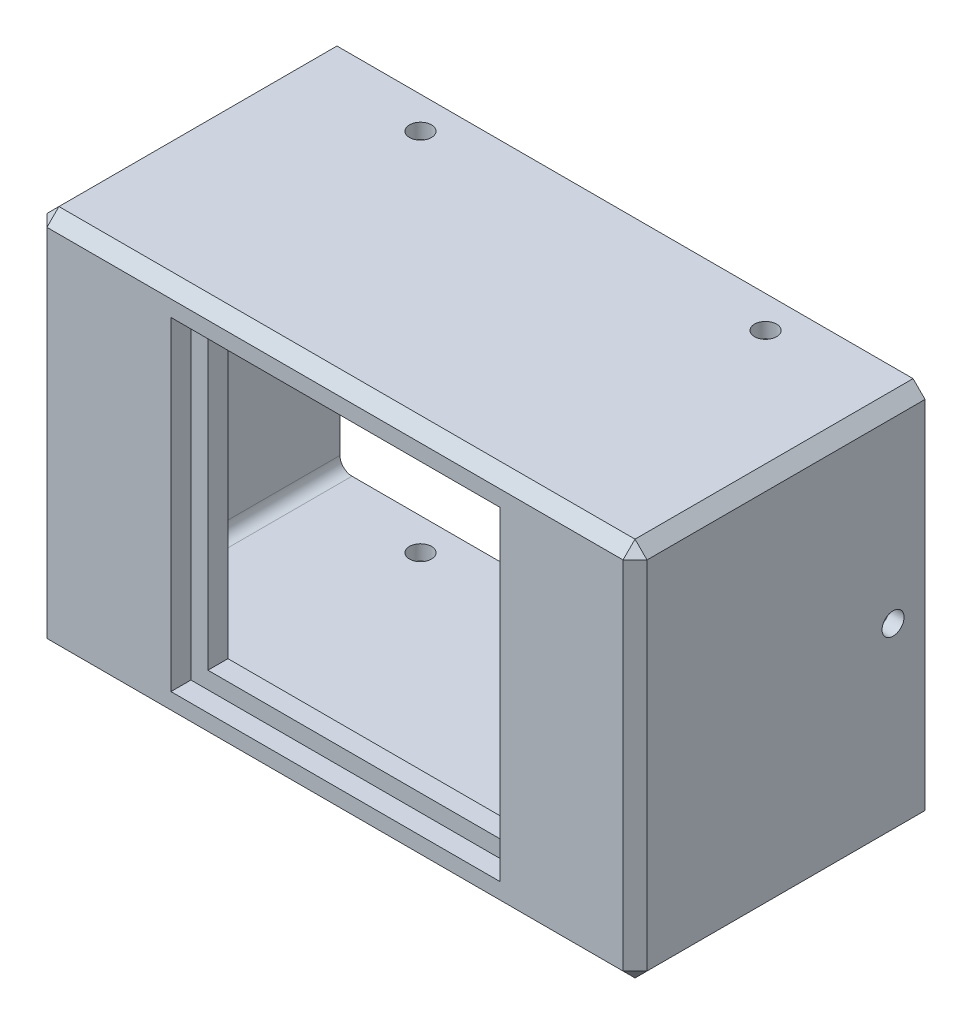
SolidWorks part; units mm, degrees
ref_plane "Plan de face" through (0, 0, 0) normal (0, 0, 1) x (1, 0, 0)
ref_plane "Plan de dessus" through (0, 0, 0) normal (0, 1, 0) x (1, 0, 0)
ref_plane "Plan de droite" through (0, 0, 0) normal (1, 0, 0) x (0, 0, -1)
sketch "Esquisse1" plane through (0, 0, 0) normal (0, 0, 1) x (1, 0, 0)
  line L1 (30, 19) -> (-30, 19)
  line L2 (30, 19) -> (30, -19)
  line L3 (30, -19) -> (-30, -19)
  line L4 (-30, 19) -> (-30, -19)
  line L5 (30, 19) -> (-30, -19) construction
  line L6 (30, -19) -> (-30, 19) construction
  point P0 (0, 0)
  point P6 (0, 0)
  dimension "D1" = 60
  dimension "D2" = 38
extrude "BASE" add sketch "Esquisse1" along normal blind 4
sketch "Esquisse2" plane through (0, 0, 4) normal (0, 0, 1) x (1, 0, 0)
  line L0 (-21.2, 0) -> (26.8, 0) construction
  line L1 (26.8, 16.5) -> (-21.2, 16.5) construction
  line L2 (26.8, 16.5) -> (26.8, -16.5) construction
  line L3 (26.8, -16.5) -> (-21.2, -16.5) construction
  line L4 (-21.2, 16.5) -> (-21.2, -16.5) construction
  line L5 (26.8, 16.5) -> (-21.2, -16.5) construction
  line L6 (26.8, -16.5) -> (-21.2, 16.5) construction
  line L7 (-14.7, 14.5) -> (14.8, 14.5)
  line L8 (-14.7, 14.5) -> (-14.7, -14.5)
  line L9 (-14.7, -14.5) -> (14.8, -14.5)
  line L10 (14.8, 14.5) -> (14.8, -14.5)
  line L11 (30, -19) -> (30, 19) construction
  point P0 (0, 0)
  dimension "D1" = 33
  dimension "D2" = 48
  dimension "D3" = 6.5
  dimension "D4" = 2
  dimension "D5" = 2
  dimension "D6" = 12
  dimension "D7" = 3.2
extrude "Screen" cut sketch "Esquisse2" against normal up to surface (4 mm away) up to face at (0, 0, 0)
sketch "Esquisse5" plane through (0, 0, 0) normal (0, 0, -1) x (-1, 0, 0)
  line L0 (2.2, 0) -> (-2.2, 0) construction
  line L1 (21.2, 16.5) -> (-26.8, 16.5) construction
  line L2 (21.2, 16.5) -> (21.2, -16.5) construction
  line L3 (21.2, -16.5) -> (-26.8, -16.5) construction
  line L4 (-26.8, 16.5) -> (-26.8, -16.5) construction
  line L5 (21.2, 16.5) -> (-26.8, -16.5) construction
  line L6 (21.2, -16.5) -> (-26.8, 16.5) construction
  line L8 (-2.8, 16.5) -> (-2.8, -16.5) construction
  circle A1 centre (-24.3, 14) radius 2.25
  circle A2 centre (-24.3, -14) radius 2.25
  circle A3 centre (18.7, -14) radius 2.25
  circle A4 centre (18.7, 14) radius 2.25
  point P0 (-0.8987, -1.3072)
  dimension "D3" = 4.5
  dimension "D1" = 48
  dimension "D2" = 33
  dimension "D4" = 2.5
  dimension "D5" = 2.5
extrude "Inserts_M3" cut sketch "Esquisse5" against normal blind 3
sketch "Esquisse6" plane through (0, 0, 0) normal (0, 0, -1) x (-1, 0, 0)
  line L0 (-28.5, 17.5) -> (-28.5, -17.5)
  line L1 (-30, 19) -> (30, 19)
  line L2 (-30, 19) -> (-30, -19)
  line L3 (-30, -19) -> (30, -19)
  line L4 (30, 19) -> (30, -19)
  line L5 (-28.5, -17.5) -> (28.5, -17.5)
  line L6 (28.5, 17.5) -> (28.5, -17.5)
  line L7 (-28.5, 17.5) -> (28.5, 17.5)
  dimension "D1" = 1.5
extrude "Walls" add sketch "Esquisse6" along normal blind 25
chamfer "Chanfrein_EXT" distance 1.2 angle 45 8 edges at (0, 19, 4) (30, 19, -10.5) (30, 0, 4) (30, -19, -10.5) (0, -19, 4) (-30, -19, -10.5) (-30, 0, 4) (-30, 19, -10.5)
fillet "Congé1" radius 1.2 8 edges at (0, 17.5, 0) (28.5, 0, 0) (-28.5, 0, 0) (0, -17.5, 0) (-28.5, -17.5, -12.5) (-28.5, 17.5, -12.5) (28.5, -17.5, -12.5) (28.5, 17.5, -12.5)
sketch "Esquisse7" plane through (30, 0, 0) normal (1, 0, 0) x (0, 0, -1)
  line L0 (25, 17.8) -> (25, -17.8) construction
  line L1 (-2.8, 17.8) -> (-2.8, -17.8) construction
  circle A0 centre (21.8, 0) radius 1.1
  point P7 (-2.8, 0)
  dimension "D1" = 2.2
  dimension "D2" = 3.2
extrude "Passage_Vis_Horizontal" cut sketch "Esquisse7" against normal through all
sketch "Esquisse9" plane through (0, 19, 0) normal (0, 1, 0) x (1, 0, 0)
  line L0 (-28.8, 25) -> (28.8, 25) construction
  line L2 (30, 25) -> (30, -2.8) construction
  line L4 (-30, -2.8) -> (-30, 25) construction
  circle A0 centre (-17.25, 21.8) radius 1.1
  circle A1 centre (17.25, 21.8) radius 1.1
  dimension "D1" = 2.2
  dimension "D2" = 3.2
  dimension "D3" = 12.75
  dimension "D4" = 12.75
extrude "Passage_Vis_Vertical" cut sketch "Esquisse9" against normal through all
sketch "Esquisse11" plane through (0, 0, 4) normal (0, 0, 1) x (1, 0, 0)
  line L1 (-16.4, 16.2) -> (16.5, 16.2)
  line L2 (-16.4, 16.2) -> (-16.4, -16.2)
  line L3 (-16.4, -16.2) -> (16.5, -16.2)
  line L4 (16.5, 16.2) -> (16.5, -16.2)
  line L6 (-14.7, 14.5) -> (-14.7, -14.5) construction
  line L7 (-14.7, -14.5) -> (14.8, -14.5) construction
  line L8 (14.8, 14.5) -> (-14.7, 14.5) construction
  line L13 (14.8, -14.5) -> (14.8, 14.5) construction
  dimension "D1" = 1.7
  dimension "D2" = 1.7
  dimension "D3" = 1.7
  dimension "D4" = 1.7
extrude "Emplacement Verre 32.5*32" cut sketch "Esquisse11" against normal blind 2 contours L2 L3 L4 L1
equation "\"D2@Esquisse11\"=\"D1@Esquisse11\""
equation "\"D3@Esquisse11\"=\"D1@Esquisse11\""
equation "\"D4@Esquisse11\"=\"D1@Esquisse11\""
